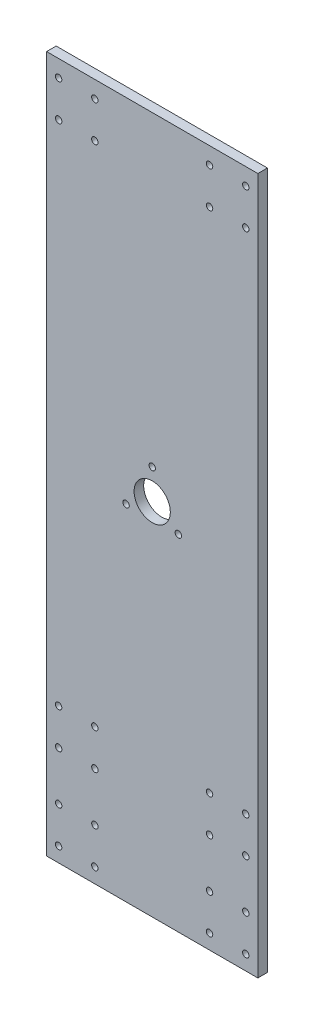
SolidWorks part; units mm, degrees
ref_plane "Front Plane" through (0, 0, 0) normal (0, 0, 1) x (1, 0, 0)
ref_plane "Top Plane" through (0, 0, 0) normal (0, 1, 0) x (1, 0, 0)
ref_plane "Right Plane" through (0, 0, 0) normal (1, 0, 0) x (0, 0, -1)
sketch "Sketch1" plane through (0, 0, 0) normal (0, 0, 1) x (1, 0, 0)
  line L0 (0, 230.825) -> (0, -230.825) construction
  line L1 (-70, -230.825) -> (70, -230.825)
  line L2 (-70, -230.825) -> (-70, 230.825)
  line L3 (-70, 230.825) -> (70, 230.825)
  line L4 (70, -230.825) -> (70, 230.825)
  line L5 (-70, -230.825) -> (70, 230.825) construction
  line L6 (-70, 230.825) -> (70, -230.825) construction
  line L7 (-70, 0) -> (70, 0) construction
  line L8 (-70, 227.65) -> (0, 227.65) construction
  line L9 (-50, 222.9386) -> (-50, 199.7908) construction
  line L12 (-63.1537, 207.65) -> (-35.7543, 207.65) construction
  line L13 (-70, -175.875) -> (72.1116, -175.875) construction
  line L15 (-70, 27.475) -> (70, 27.475) construction
  line L16 (-70, -175.875) -> (70, -175.875) construction
  line L18 (-70, -180.875) -> (70, -180.875) construction
  circle A9 centre (-62, 219.65) radius 2.125
  circle A11 centre (-38, 219.65) radius 2.125
  circle A12 centre (-38, 195.65) radius 2.125
  circle A13 centre (-62, 195.65) radius 2.125
  circle A14 centre (38, 195.65) radius 2.125
  circle A15 centre (62, 195.65) radius 2.125
  circle A16 centre (38, 219.65) radius 2.125
  circle A17 centre (62, 219.65) radius 2.125
  circle A26 centre (62, -164.7) radius 2.125
  circle A27 centre (38, -164.7) radius 2.125
  circle A28 centre (62, -140.7) radius 2.125
  circle A29 centre (38, -140.7) radius 2.125
  circle A30 centre (-62, -140.7) radius 2.125
  circle A31 centre (-38, -140.7) radius 2.125
  circle A32 centre (-38, -164.7) radius 2.125
  circle A33 centre (-62, -164.7) radius 2.125
  circle A34 centre (-62, -197.05) radius 2.125
  circle A35 centre (-38, -197.05) radius 2.125
  circle A36 centre (-38, -221.05) radius 2.125
  circle A37 centre (-62, -221.05) radius 2.125
  circle A38 centre (38, -221.05) radius 2.125
  circle A39 centre (62, -221.05) radius 2.125
  circle A40 centre (38, -197.05) radius 2.125
  circle A41 centre (62, -197.05) radius 2.125
  point P0 (0, 0)
  dimension "D4" = 4.25
  dimension "D6" = 8
  dimension "D7" = 12
  dimension "D9" = 406.7
  dimension "D11" = 11.175
  dimension "D12" = 5
  dimension "D1" = 461.65
  dimension "D2" = 140
  dimension "D3" = 3.175
  dimension "D5" = 8
  dimension "D8" = 12
  dimension "D10" = 203.35
extrude "Boss-Extrude1" add sketch "Sketch1" along normal blind 6.35
sketch "Sketch2" plane through (0, 0, 6.35) normal (0, 0, 1) x (1, 0, 0)
  line L0 (-70, -167.525) -> (70, -167.525) construction
  line L1 (-70, 230.825) -> (-70, -230.825) construction
  line L2 (70, -230.825) -> (70, 230.825) construction
  line L3 (70, 230.825) -> (-70, 230.825) construction
  line L4 (-70, 7.475) -> (70, 7.475) construction
  circle A0 centre (0, 7.475) radius 12
  circle A1 centre (0, 27.475) radius 2.125
  circle A2 centre (17.3205, -2.525) radius 2.125
  circle A3 centre (-17.3205, -2.525) radius 2.125
  point P20 (0, 0)
  point P22 (0, 7.475)
  dimension "D3" = 4.25
  dimension "D6" = 24
  dimension "D1" = 398.35
  dimension "D2" = 175
  dimension "D4" = 20
  dimension "D5" = 3
extrude "Cut-Extrude1" cut sketch "Sketch2" against normal through all
